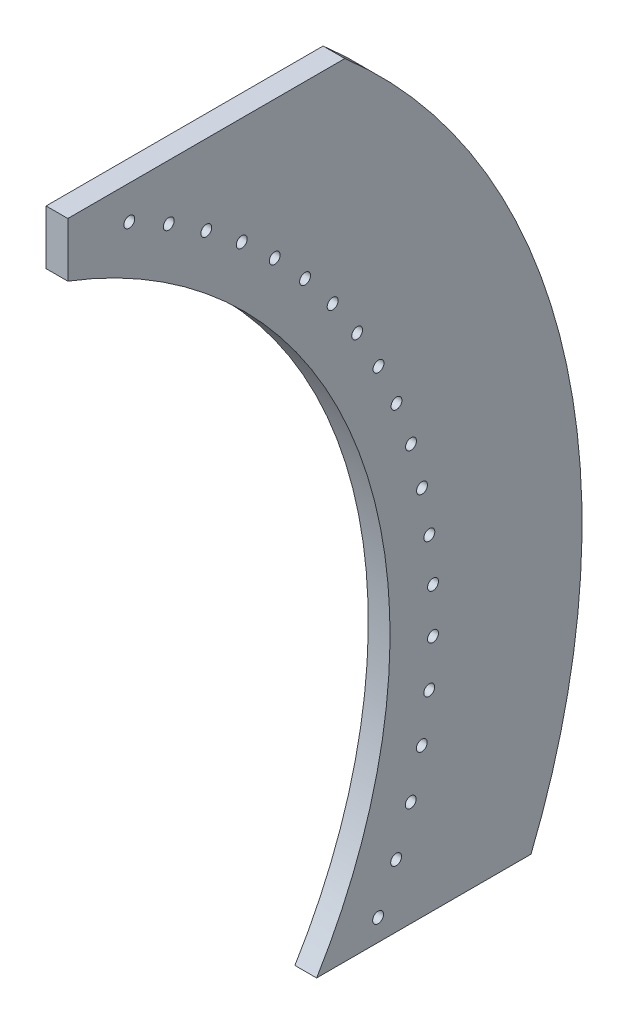
SolidWorks part; units mm, degrees
ref_plane "Front Plane" through (0, 0, 0) normal (0, 0, 1) x (1, 0, 0)
ref_plane "Top Plane" through (0, 0, 0) normal (0, 1, 0) x (1, 0, 0)
ref_plane "Right Plane" through (0, 0, 0) normal (1, 0, 0) x (0, 0, -1)
sketch "Sketch1" plane through (0, 0, 0) normal (1, 0, 0) x (0, 0, -1)
  line L0 (0, 609.6) -> (323.85, 609.6)
  line L1 (323.85, 609.6) -> (323.85, 0)
  line L2 (323.85, 0) -> (0, 0)
  line L3 (0, 609.6) -> (0, 577.85)
  line L4 (0, 0) -> (0, 31.75)
  arc A1 (0, 577.85) -> (0, 31.75) centre (-103.7599, 304.8) cw
  dimension "D4" = 292.1
  dimension "D1" = 609.6
  dimension "D2" = 323.85
  dimension "D3" = 546.1
extrude "Boss-Extrude1" add sketch "Sketch1" along normal blind 12.7
sketch "Sketch2" plane through (12.7, 0, 0) normal (1, 0, 0) x (0, 0, -1)
  line L0 (0, 0) -> (323.85, 0) construction
  line L1 (-233.5002, 152.4) -> (618.8069, 152.4)
  line L2 (-233.5002, 152.4) -> (-233.5002, 0)
  line L3 (-233.5002, 0) -> (618.8069, 0)
  line L4 (618.8069, 152.4) -> (618.8069, 0)
  dimension "D1" = 152.4
  dimension "D2" = 0
extrude "Cut-Extrude1" cut sketch "Sketch2" against normal blind 12.7
sketch "Sketch3" plane through (12.7, 0, 0) normal (1, 0, 0) x (0, 0, -1)
  line L0 (323.85, 609.6) -> (0, 609.6) construction
  line L1 (323.85, 152.4) -> (145.4321, 152.4) construction
  line L2 (270.7608, 152.4) -> (323.85, 152.4)
  line L3 (323.85, 152.4) -> (323.85, 609.6)
  line L4 (323.85, 609.6) -> (161.925, 609.6)
  arc A0 (161.925, 609.6) -> (270.7608, 152.4) centre (-103.7599, 304.8) cw
extrude "Cut-Extrude2" cut sketch "Sketch3" against normal blind 12.7
hole_wizard "1/4 (0.25) Diameter Hole1" positions "Sketch4" profile "Sketch5" hole size "1/4" standard "ANSI Inch" end condition through all
sketch "Sketch4" plane through (12.7, 0, 0) normal (1, 0, 0) x (0, 0, -1)
  line L0 (270.7608, 152.4) -> (145.4321, 152.4) construction
  arc A0 (145.4321, 152.4) -> (0, 577.85) centre (-103.7599, 304.8) ccw construction
  circle A1 centre (-103.7599, 304.8) radius 317.5 construction
  point P0 (181.3544, 165.1)
  point P26 (191.917, 189.1217)
  point P27 (200.4597, 213.9336)
  point P28 (206.9243, 239.3662)
  point P29 (211.2667, 265.2458)
  point P30 (213.4571, 291.3956)
  point P31 (213.4805, 317.6369)
  point P32 (211.3369, 343.7906)
  point P33 (207.0409, 369.6779)
  point P34 (200.6218, 395.122)
  point P35 (192.1234, 419.9492)
  point P36 (181.6039, 443.9897)
  point P37 (169.135, 467.0795)
  point P38 (154.802, 489.0607)
  point P39 (138.7028, 509.7832)
  point P40 (120.9473, 529.1055)
  point P41 (101.6568, 546.8955)
  point P42 (80.9631, 563.0318)
  point P43 (59.0076, 577.4041)
  point P44 (35.9401, 589.9143)
  dimension "D1" = 12.7
  dimension "D2" = 317.5
  dimension "D3" = 20
sketch "Sketch5" plane through (12.7, 165.1, -181.3544) normal (0, 1, 0) x (0, 0, -1)
  line L0 (0, 0) -> (0, 12.7)
  line L1 (0, 12.7) -> (3.175, 12.7)
  line L2 (3.175, 12.7) -> (3.175, 0)
  line L5 (3.175, 0) -> (0, 0)
  line L11 (0, -6.35) -> (0, 107.95) construction
  dimension "Thru Hole Dia." = 6.35
  dimension "Thru Hole Depth" = 12.7
